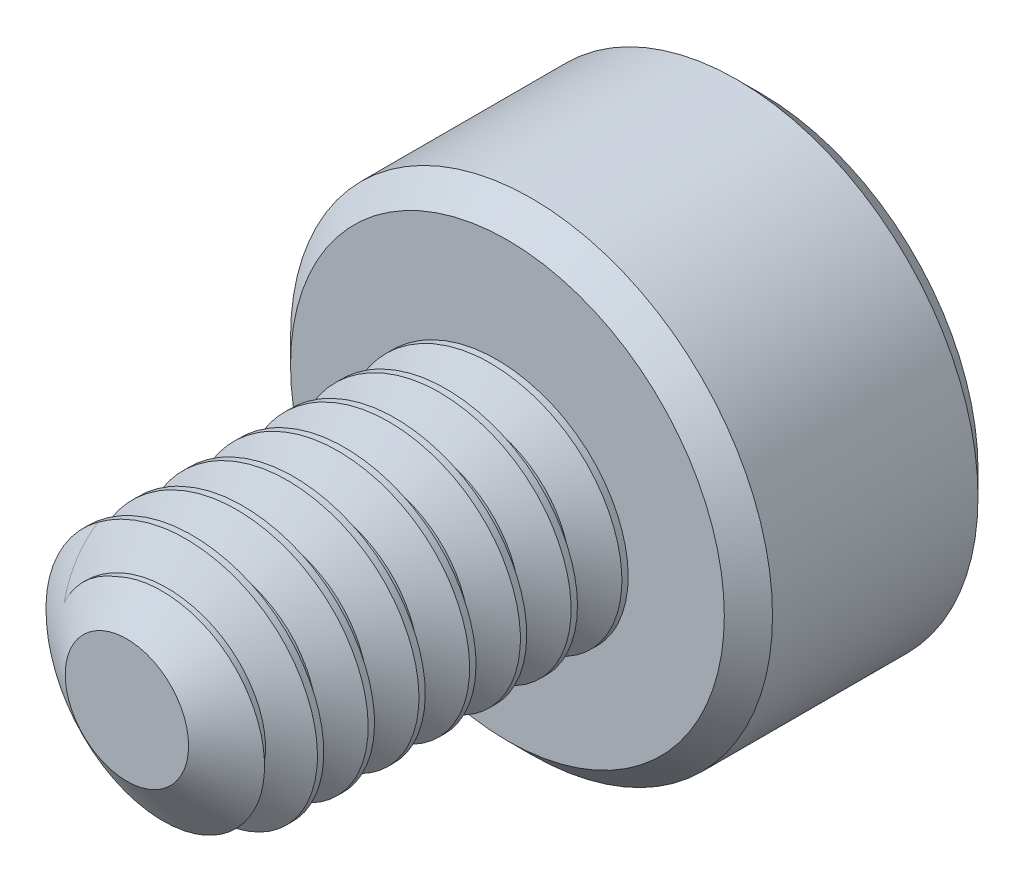
SolidWorks part; units mm, degrees
ref_plane "Front Plane" through (0, 0, 0) normal (0, 0, 1) x (1, 0, 0)
ref_plane "Top Plane" through (0, 0, 0) normal (0, 1, 0) x (1, 0, 0)
ref_plane "Right Plane" through (0, 0, 0) normal (1, 0, 0) x (0, 0, -1)
sketch "Sketch1" plane through (0, 0, 0) normal (0, 0, 1) x (1, 0, 0)
  circle A0 centre (0, 0) radius 1
  dimension "OD" = 2
extrude "Extrude1" add sketch "Sketch1" against normal blind 3
sketch "Sketch2" plane through (0, 0, 0) normal (0, 0, 1) x (1, 0, 0)
  circle A0 centre (0, 0) radius 1 construction
  circle A1 centre (0, 0) radius 1
curve "Helix/Spiral1" pitch 0.4 height 3.4 radius 1 centre (0, 0, 0) axis (0, 0, -1) start towards (0, 1, 0) parameters "pitch"=0.4
sketch "Sketch3" plane through (0, 0, 0) normal (1, 0, 0) x (0, 0, -1)
  line L0 (-0.35, 1) -> (-0.2, 0.7402)
  line L1 (-0.2, 0.7402) -> (-0.15, 0.7402)
  line L2 (-0.15, 0.7402) -> (0, 1)
  line L3 (-0.35, 1) -> (0, 1)
  line L4 (-0.175, 1) -> (-0.175, 0.7402) construction
  line L5 (-0.275, 0.8701) -> (-0.075, 0.8701) construction
  line L6 (0, 1) -> (0, -1) construction
  dimension "D1" = 0.05
  dimension "D2" = 0.2
  dimension "D3" = 60
sweep "Cut-Sweep1" cut profiles "Sketch3" path "Helix/Spiral1" align with end faces yes
sketch "Sketch4" plane through (0, 0, 0) normal (1, 0, 0) x (0, 0, -1)
  line L0 (0.3598, 1) -> (0, 0.4862)
  line L1 (0, 0.4862) -> (0, 1)
  line L2 (0.3598, 1) -> (0, 1)
  line L3 (-0.35, 1) -> (0, 1) construction
  line L4 (0, 0) -> (7.0209, 0) construction
  dimension "D1" = 55
  dimension "D2" = 0.254
revolve "Cut-Revolve1" cut sketch "Sketch4" angle 360 about L4
sketch "Sketch6" plane through (0, 0, -3) normal (0, 0, -1) x (-1, 0, 0)
  circle A0 centre (0, 0) radius 1.9
  dimension "head dia" = 3.8
extrude "Extrude2" add sketch "Sketch6" along normal blind 2
sketch "Sketch7" plane through (0, 0, -5) normal (0, 0, -1) x (-1, 0, 0)
  line L1 (0, 0.866) -> (-0.75, 0.433)
  line L2 (-0.75, 0.433) -> (-0.75, -0.433)
  line L3 (-0.75, -0.433) -> (0, -0.866)
  line L4 (0, -0.866) -> (0.75, -0.433)
  line L5 (0.75, -0.433) -> (0.75, 0.433)
  line L6 (0.75, 0.433) -> (0, 0.866)
  circle A0 centre (0, 0) radius 0.75 construction
  dimension "hex dia" = 1.5
extrude "Cut-Extrude1" cut sketch "Sketch7" against normal blind 1.125
sketch "Sketch8" plane through (0, 0, -5) normal (0, 0, -1) x (-1, 0, 0)
  circle A0 centre (0, 0) radius 0.866
extrude "Cut-Extrude2" cut sketch "Sketch8" against normal through all draft 45
chamfer "Chamfer1" distance 0.19 angle 45 2 edges at (-1.9, 0, -5) (-1.9, 0, -3)
sketch "Sketch10" plane through (0, 0, -3) normal (0, 0, 1) x (1, 0, 0)
  circle A1 centre (0, 0) radius 1
  circle A2 centre (0, 0) radius 1
  dimension "D1" = 0
ref_plane "Plane1" through (0, 0, 0) normal (0, 0, 1) x (1, 0, 0)
extrude "partial thread" [suppressed] add sketch "Sketch10" along normal up to surface (2 mm away) separate body up to plane "Plane1"
chamfer "Chamfer2" [suppressed] distance 0.04 angle 45
combine bodies "Combine1" [suppressed] operation type add bodies to combine 107 108
sketch "Sketch9" plane through (0, 0, 0) normal (1, 0, 0) x (0, 0, -1)
  line L0 (0, 1) -> (0, -1) construction
  line L1 (1, 1) -> (1, -1) construction
  dimension "D1" = 1
equation "\"D3@Helix/Spiral1\" = \"screw length@Extrude1\"+\"pitch@Helix/Spiral1\""
equation "\"D1@Sketch3\" = \"pitch@Helix/Spiral1\"*.125"
equation "\"D2@Sketch3\" = \"pitch@Helix/Spiral1\"*.5"
equation "\"D1@Cut-Extrude1\" = \"hex dia@Sketch7\"*.75"
equation "\"D1@Chamfer1\" = \"head dia@Sketch6\"*.05"
equation "\"D1@Sketch9\" = \"pitch@Helix/Spiral1\"*2.5"
equation "\"D1@Chamfer2\"=\"OD@Sketch1\"*.02"
